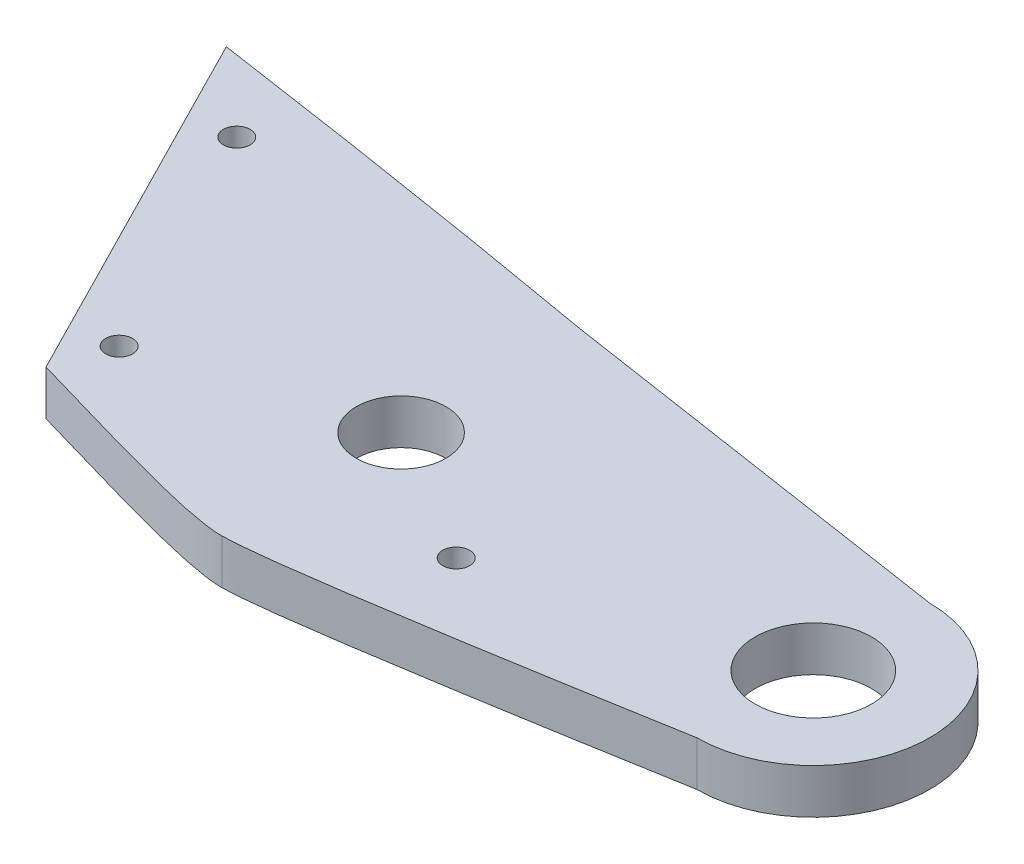
SolidWorks part; units mm, degrees
ref_plane "Front Plane" through (0, 0, 0) normal (0, 0, 1) x (1, 0, 0)
ref_plane "Top Plane" through (0, 0, 0) normal (0, 1, 0) x (1, 0, 0)
ref_plane "Right Plane" through (0, 0, 0) normal (1, 0, 0) x (0, 0, -1)
sketch "Sketch1" plane through (0, 0, 0) normal (0, 1, 0) x (1, 0, 0)
  line L0 (0, 0) -> (-300, 0) construction
  line L1 (0, 0) -> (46, 0) construction
  line L2 (-300, 0) -> (-300, 40) construction
  line L3 (-328.2843, 28.2843) -> (-271.7157, -28.2843) construction
  circle A0 centre (0, 0) radius 5
  circle A1 centre (46, 0) radius 6.5
  circle A2 centre (-300, 0) radius 40
  circle A3 centre (0, 0) radius 20
  circle A4 centre (46, 0) radius 13
  spline S0 degree 3 poles (-271.7157, -28.2843) (-189.2199, 54.2115) (-20, -20) (0, -20) knots 0 0 0 0 1 1 1 1
  spline S1 degree 3 poles (-328.2843, 28.2843) (-300, 56.5685) (-114.8731, 40.3783) (0, 20) knots 0 0 0 0 1 1 1 1
  spline S2 degree 2 poles (0, -20) (5.9085, -20) (46, -13) knots 0 0 0 1 1 1
  spline S3 degree 2 poles (0, 20) (0.0315, 20) (46, 13) knots 0 0 0 1 1 1
  dimension "D3" = 10
  dimension "D4" = 13
  dimension "D5" = 80
  dimension "D6" = 40
  dimension "D7" = 45
  dimension "D8" = 120
  dimension "D9" = 350
  dimension "D10" = 350
  dimension "D11" = 60
  dimension "D12" = 26
  dimension "D1" = 46
  dimension "D2" = 300
extrude "Boss-Extrude1" add sketch "Sketch1" along normal blind 20 and the other way blind 20 contours S1 A2 | S1 A2 S0 A3 | S3 A3 S0 A0 | S3 A3 S2 A4 | A4 A1 region at (-299.9271, 0, 0.2395) region at (-151.7179, 0, -19.1123) region at (-19.1932, 0, -3.0516) region at (26.0397, 0, 0.3418) region at (54.9324, 0, -8.9324)
ref_plane "Plane2" through (0, 20, 0) normal (0, 1, 0) x (1, 0, 0)
sketch "Sketch5" plane through (0, 20, 0) normal (0, 1, 0) x (1, 0, 0)
  line L0 (-47.037, 27.5275) -> (92.1208, 16.1646)
  line L1 (92.1208, 16.1646) -> (85.7247, -16.9188)
  line L2 (85.7247, -16.9188) -> (-17.2628, -30.9078)
  line L3 (-17.2628, -30.9078) -> (-47.037, 27.5275)
  line L4 (0, 0) -> (0, 89.1393) construction
  spline S0 degree 3 poles (-328.2843, 28.2843) (-300, 56.5685) (-114.8731, 40.3783) (0, 20) knots 0 0 0 0 1 1 1 1 construction
  dimension "D1" = 27
  dimension "D2" = 54.5
extrude "Cut-Extrude4" cut sketch "Sketch5" against normal blind 35
sketch "Sketch6" plane through (0, -20, 0) normal (0, -1, 0) x (-1, 0, 0)
  circle A1 centre (24.0759, -7.393) radius 1.5
  circle A2 centre (-15.2015, -9.0529) radius 1.5
  circle A3 centre (37.7138, 19.373) radius 1.5
  dimension "D1" = 3
extrude "Cut-Extrude5" cut sketch "Sketch6" against normal blind 10
sketch "Sketch7" plane through (0, 20, 0) normal (0, 1, 0) x (1, 0, 0)
  line L0 (-47.037, 27.5275) -> (-26.1377, -13.4898)
  line L1 (-26.1377, -13.4898) -> (-379.5957, -92.5802)
  line L2 (-379.5957, -92.5802) -> (-321.5056, 137.2547)
  line L3 (-321.5056, 137.2547) -> (-47.037, 27.5275)
extrude "Cut-Extrude6" cut sketch "Sketch7" against normal blind 50
